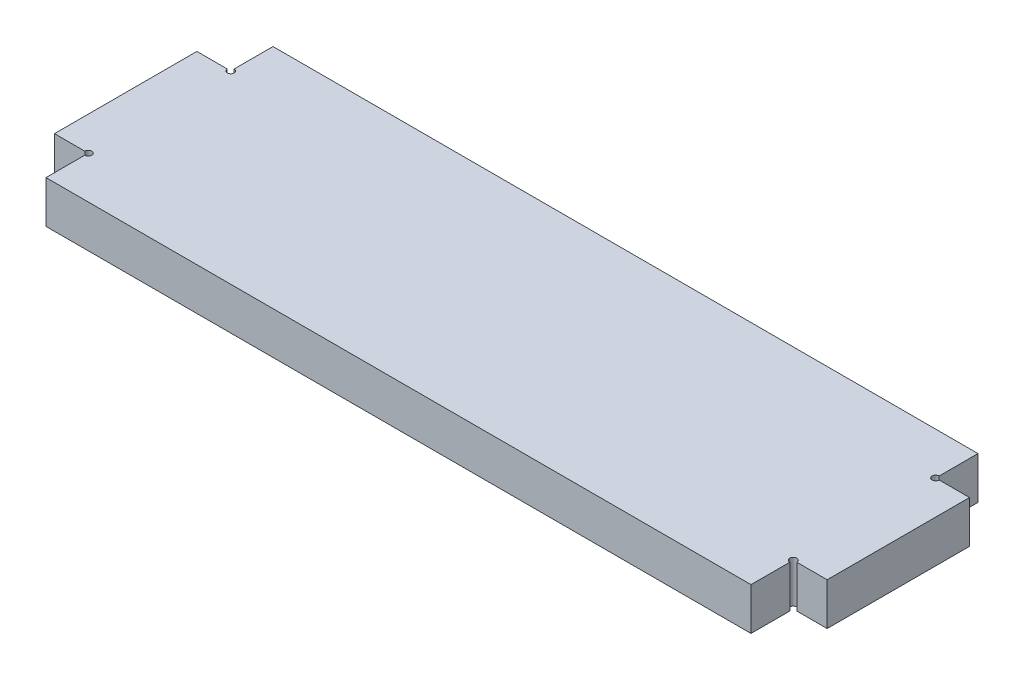
SolidWorks part; units mm, degrees
ref_plane "Front Plane" through (0, 0, 0) normal (0, 0, 1) x (1, 0, 0)
ref_plane "Top Plane" through (0, 0, 0) normal (0, 1, 0) x (1, 0, 0)
ref_plane "Right Plane" through (0, 0, 0) normal (1, 0, 0) x (0, 0, -1)
sketch "Sketch1" plane through (0, 0, 0) normal (0, 1, 0) x (1, 0, 0)
  line L0 (0.25, 5.3321) -> (2.4, 5.3321)
  line L1 (2.4, 5.3321) -> (2.4, -4.7679)
  line L2 (2.4, -4.7679) -> (0.25, -4.7679)
  line L3 (0, -5.0179) -> (0, -7.7679)
  line L4 (0, -7.7679) -> (-50, -7.7679)
  line L5 (0, 5.5821) -> (0, 8.3321)
  line L6 (0, 8.3321) -> (-50, 8.3321)
  line L7 (-50, 8.3321) -> (-50, 5.5774)
  line L8 (-50.2453, 5.3321) -> (-52.4, 5.3321)
  line L9 (-50, -7.7679) -> (-50, -5.0179)
  line L10 (-50.25, -4.7679) -> (-52.4, -4.7679)
  line L11 (-52.4, -4.7679) -> (-52.4, 5.3321)
  arc A0 (-50.2453, 5.3321) -> (-50, 5.5774) centre (-50, 5.3321) ccw
  arc A1 (-50, -5.0179) -> (-50.25, -4.7679) centre (-50, -4.7679) ccw
  arc A2 (0.25, -4.7679) -> (0, -5.0179) centre (0, -4.7679) ccw
  arc A3 (0, 5.5821) -> (0.25, 5.3321) centre (0, 5.3321) ccw
  dimension "D1" = 10.1
  dimension "D2" = 2.4
  dimension "D3" = 3
  dimension "D4" = 3
  dimension "D5" = 50
  dimension "D6" = 50
  dimension "D7" = 2.4
extrude "Boss-Extrude1" add sketch "Sketch1" along normal blind 3 contours L6 L7 A0 L8 L11 L10 A1 L9 L4 L3 A2 L2 L1 L0 A3 L5
